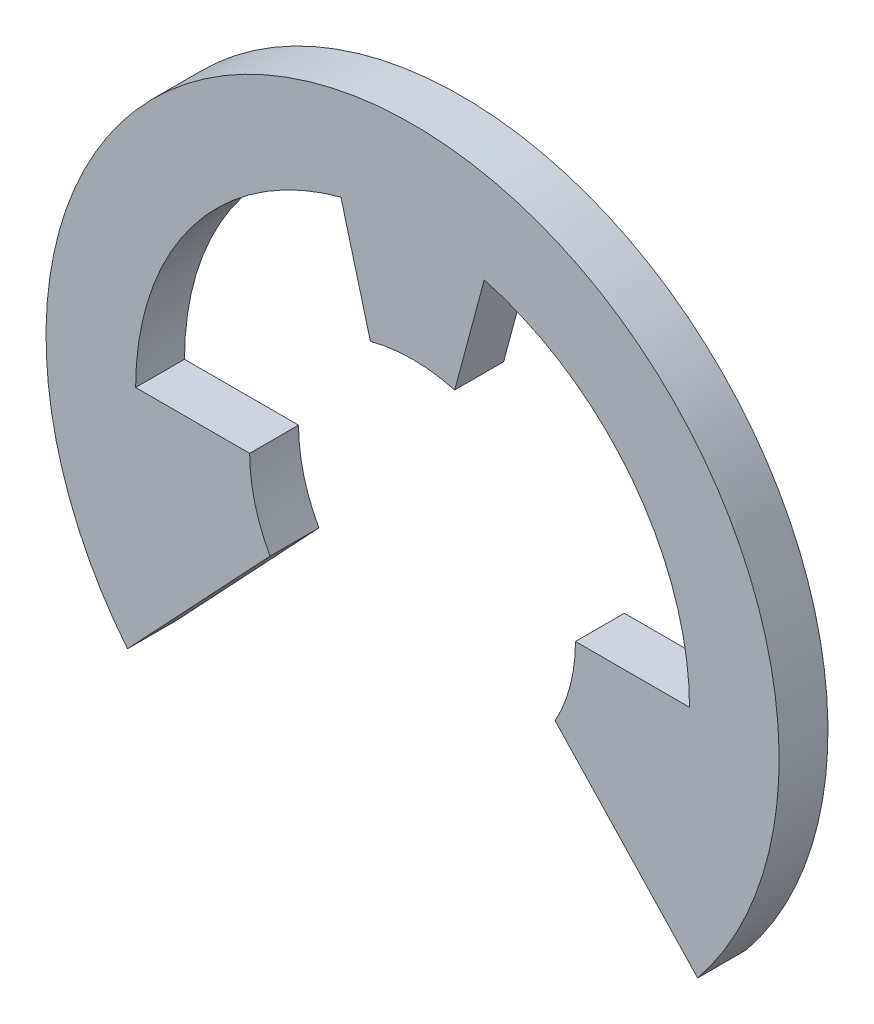
SolidWorks part; units mm, degrees
ref_plane "前基準面" through (0, 0, 0) normal (0, 0, 1) x (1, 0, 0)
ref_plane "上基準面" through (0, 0, 0) normal (0, 1, 0) x (1, 0, 0)
ref_plane "右基準面" through (0, 0, 0) normal (1, 0, 0) x (0, 0, -1)
sketch "草圖1" plane through (0, 0, 0) normal (0, 0, 1) x (1, 0, 0)
  line L0 (-3.5, -2.8284) -> (-1.75, -0.9682)
  line L1 (-2, 0) -> (-3.4, 0)
  line L2 (-0.88, 3.2841) -> (-0.5176, 1.9319)
  line L3 (0.5176, 1.9319) -> (0.88, 3.2841)
  line L4 (3.4, 0) -> (2, 0)
  line L5 (1.75, -0.9682) -> (3.5, -2.8284)
  arc A0 (3.5, -2.8284) -> (-3.5, -2.8284) centre (0, 0) ccw
  arc A1 (-1.75, -0.9682) -> (-2, 0) centre (0, 0) cw
  arc A2 (-3.4, 0) -> (-0.88, 3.2841) centre (0, 0) cw
  arc A3 (-0.5176, 1.9319) -> (0.5176, 1.9319) centre (0, 0) cw
  arc A4 (0.88, 3.2841) -> (3.4, 0) centre (0, 0) cw
  arc A5 (2, 0) -> (1.75, -0.9682) centre (0, 0) cw
extrude "填料-伸長1" add sketch "草圖1" against normal blind 0.3 and the other way blind 0.3
ref_plane "平面4" through (0, 0, 0.3) normal (0, 0, 1) x (1, 0, 0)
ref_plane "ring_to_screw XY" through (0, 0, 0) normal (0, 0, 1) x (1, 0, 0)
ref_plane "ring_to_screw XZ" through (0, 0, 0) normal (0, -1, 0) x (-1, 0, 0)
ref_plane "ring_to_screw YZ" through (0, 0, 0) normal (1, 0, 0) x (0, 0, -1)
ref_axis "ring_to_screw X" through (-80.9, 0, 0) along (1, 0, 0)
ref_axis "ring_to_screw Y" through (0, -50, 0) along (0, 1, 0)
ref_axis "ring_to_screw Z" through (0, 0, 80.9) along (0, 0, -1)
sketch3d "ring_to_screw"
  point P0 (0, 0, 0)
ref_plane "COMBINATION_MODULE XY" through (0, 0, 0.3) normal (0, 0, 1) x (1, 0, 0)
ref_plane "COMBINATION_MODULE XZ" through (0, 0, 0) normal (0, -1, 0) x (-1, 0, 0)
ref_plane "COMBINATION_MODULE YZ" through (0, 0, 0) normal (1, 0, 0) x (0, 0, -1)
ref_axis "COMBINATION_MODULE X" through (-80.9, 0, 0.3) along (1, 0, 0)
ref_axis "COMBINATION_MODULE Y" through (0, -50, 0.3) along (0, 1, 0)
ref_axis "COMBINATION_MODULE Z" through (0, 0, 80.9) along (0, 0, -1)
sketch3d "COMBINATION_MODULE"
  point P0 (0, 0, 0.3)
